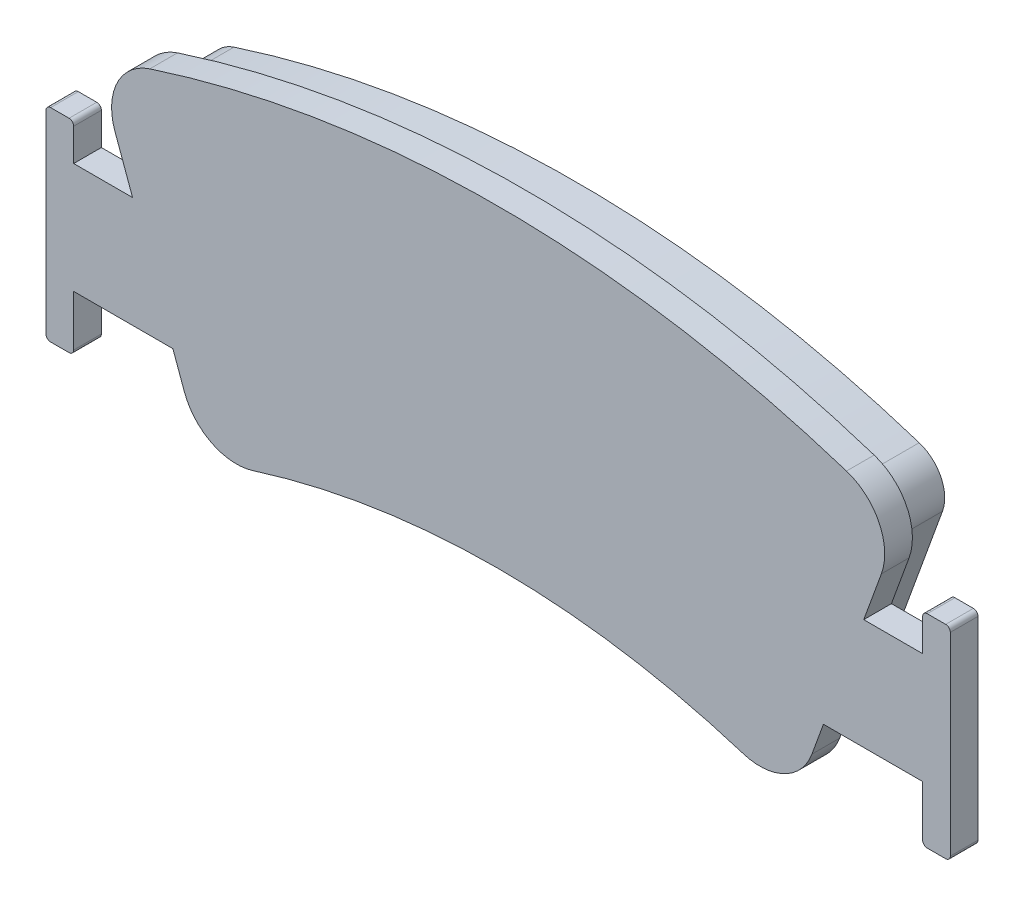
SolidWorks part; units mm, degrees
ref_plane "Płaszczyzna przednia" through (0, 0, 0) normal (0, 0, 1) x (1, 0, 0)
ref_plane "Płaszczyzna górna" through (0, 0, 0) normal (0, 1, 0) x (1, 0, 0)
ref_plane "Płaszczyzna prawa" through (0, 0, 0) normal (1, 0, 0) x (0, 0, -1)
sketch "Szkic1" plane through (0, 0, 0) normal (0, 0, 1) x (1, 0, 0)
  line L0 (-3.3117, 84.9355) -> (-2.9977, 76.8831)
  line L1 (0.9603, 74.1578) -> (23.3617, 81.7266)
  line L2 (57.7167, 62.4002) -> (52.2449, 56.4843)
  line L3 (53.1165, 51.7585) -> (74.3086, 41.2702)
  line L4 (84.9355, 3.3117) -> (76.8831, 2.9977)
  line L5 (74.1578, -0.9603) -> (81.7266, -23.3617)
  line L6 (62.4002, -57.7167) -> (56.4843, -52.2449)
  line L7 (51.7585, -53.1165) -> (41.2702, -74.3086)
  line L8 (3.3117, -84.9355) -> (2.9977, -76.8831)
  line L9 (-0.9603, -74.1578) -> (-23.3617, -81.7266)
  line L10 (-57.7167, -62.4002) -> (-52.2449, -56.4843)
  line L11 (-53.1165, -51.7585) -> (-74.3086, -41.2702)
  line L12 (-84.9355, -3.3117) -> (-76.8831, -2.9977)
  line L13 (-74.1578, 0.9603) -> (-81.7266, 23.3617)
  line L14 (-62.4002, 57.7167) -> (-56.4843, 52.2449)
  line L15 (-51.7585, 53.1165) -> (-41.2702, 74.3086)
  line L16 (0.9603, 74.1578) -> (-1.6342, 73.1454)
  line L17 (-2.9977, 74.077) -> (-2.9977, 76.8831)
  line L18 (53.1165, 51.7585) -> (50.5661, 52.8772)
  line L19 (50.2606, 54.5001) -> (52.2449, 56.4843)
  line L20 (74.1578, -0.9603) -> (73.1454, 1.6342)
  line L21 (74.077, 2.9977) -> (76.8831, 2.9977)
  line L22 (51.7585, -53.1165) -> (52.8772, -50.5661)
  line L23 (54.5001, -50.2606) -> (56.4843, -52.2449)
  line L24 (-0.9603, -74.1578) -> (1.6342, -73.1454)
  line L25 (2.9977, -74.077) -> (2.9977, -76.8831)
  line L26 (-53.1165, -51.7585) -> (-50.5661, -52.8772)
  line L27 (-50.2606, -54.5001) -> (-52.2449, -56.4843)
  line L28 (-74.1578, 0.9603) -> (-73.1454, -1.6342)
  line L29 (-74.077, -2.9977) -> (-76.8831, -2.9977)
  line L30 (-51.7585, 53.1165) -> (-52.8772, 50.5661)
  line L31 (-54.5001, 50.2606) -> (-56.4843, 52.2449)
  line L32 (-3.2338, 82.937) -> (-2.9977, 76.8831)
  line L33 (19.9378, 80.5697) -> (15.0444, 78.9164)
  line L34 (0.9603, 74.1578) -> (5.5705, 75.7155)
  line L35 (44.0396, 59.8465) -> (26.6236, 49.8436)
  line L36 (22.133, 52.2992) -> (21.2067, 71.3197)
  line L37 (25.5267, 74.1578) -> (43.8691, 65.1401)
  line L38 (70.4876, 34.3874) -> (77.0812, 15.0409)
  line L39 (73.4586, 11.1771) -> (54.0705, 16.4191)
  line L40 (52.6315, 21.3307) -> (65.426, 35.4352)
  line L41 (74.1578, -25.5267) -> (65.1401, -43.8691)
  line L42 (59.8465, -44.0396) -> (49.8436, -26.6236)
  line L43 (52.2992, -22.133) -> (71.3197, -21.2067)
  line L44 (34.3874, -70.4876) -> (15.0409, -77.0812)
  line L45 (11.1771, -73.4586) -> (16.4191, -54.0705)
  line L46 (21.3307, -52.6315) -> (35.4352, -65.426)
  line L47 (-25.5267, -74.1578) -> (-43.8691, -65.1401)
  line L48 (-44.0396, -59.8465) -> (-26.6236, -49.8436)
  line L49 (-22.133, -52.2992) -> (-21.2067, -71.3197)
  line L50 (-70.4876, -34.3874) -> (-77.0812, -15.0409)
  line L51 (-73.4586, -11.1771) -> (-54.0705, -16.4191)
  line L52 (-52.6315, -21.3307) -> (-65.426, -35.4352)
  line L53 (-74.1578, 25.5267) -> (-65.1401, 43.8691)
  line L54 (-59.8465, 44.0396) -> (-49.8436, 26.6236)
  line L55 (-52.2992, 22.133) -> (-71.3197, 21.2067)
  line L56 (-34.3874, 70.4876) -> (-15.0409, 77.0812)
  line L57 (-11.1771, 73.4586) -> (-16.4191, 54.0705)
  line L58 (-21.3307, 52.6315) -> (-35.4352, 65.426)
  circle A0 centre (0, 0) radius 120
  arc A2 (-62.4002, 57.7167) -> (-81.7266, 23.3617) centre (0, 0) ccw
  circle A3 centre (0, 50) radius 7
  circle A4 centre (50, 0) radius 7
  circle A5 centre (0, -50) radius 7
  circle A6 centre (-50, 0) radius 7
  circle A7 centre (0, 0) radius 35
  circle A8 centre (10.3075, 77.316) radius 5
  circle A9 centre (61.9591, 47.3822) radius 5
  circle A10 centre (77.316, -10.3075) radius 5
  circle A11 centre (47.3822, -61.9591) radius 5
  circle A12 centre (-10.3075, -77.316) radius 5
  circle A13 centre (-61.9591, -47.3822) radius 5
  circle A14 centre (-77.316, 10.3075) radius 5
  circle A15 centre (-47.3822, 61.9591) radius 5
  arc A16 (-2.9977, 76.8831) -> (0.9603, 74.1578) centre (0, 77) ccw
  arc A17 (52.2449, 56.4843) -> (53.1165, 51.7585) centre (54.4472, 54.4472) ccw
  arc A18 (76.8831, 2.9977) -> (74.1578, -0.9603) centre (77, 0) ccw
  arc A19 (56.4843, -52.2449) -> (51.7585, -53.1165) centre (54.4472, -54.4472) ccw
  arc A20 (2.9977, -76.8831) -> (-0.9603, -74.1578) centre (0, -77) ccw
  arc A21 (-52.2449, -56.4843) -> (-53.1165, -51.7585) centre (-54.4472, -54.4472) ccw
  arc A22 (-76.8831, -2.9977) -> (-74.1578, 0.9603) centre (-77, 0) ccw
  arc A23 (-56.4843, 52.2449) -> (-51.7585, 53.1165) centre (-54.4472, 54.4472) ccw
  arc A24 (-84.9355, -3.3117) -> (-74.3086, -41.2702) centre (0, 0) ccw
  arc A25 (-57.7167, -62.4002) -> (-23.3617, -81.7266) centre (0, 0) ccw
  arc A26 (3.3117, -84.9355) -> (41.2702, -74.3086) centre (0, 0) ccw
  arc A27 (62.4002, -57.7167) -> (81.7266, -23.3617) centre (0, 0) ccw
  arc A28 (84.9355, 3.3117) -> (74.3086, 41.2702) centre (0, 0) ccw
  arc A29 (57.7167, 62.4002) -> (23.3617, 81.7266) centre (0, 0) ccw
  arc A30 (-3.3117, 84.9355) -> (-41.2702, 74.3086) centre (0, 0) ccw
  arc A31 (19.9378, 80.5697) -> (56.3587, 60.9319) centre (0, 0) cw
  arc A32 (-1.6342, 73.1454) -> (-2.9977, 74.077) centre (-1.9977, 74.077) cw
  arc A33 (50.5661, 52.8772) -> (50.2606, 54.5001) centre (50.9678, 53.793) cw
  arc A34 (71.0696, 42.8732) -> (82.937, 3.2338) centre (0, 0) cw
  arc A35 (73.1454, 1.6342) -> (74.077, 2.9977) centre (74.077, 1.9977) cw
  arc A36 (80.5697, -19.9378) -> (60.9319, -56.3587) centre (0, 0) cw
  arc A37 (52.8772, -50.5661) -> (54.5001, -50.2606) centre (53.793, -50.9678) cw
  arc A38 (42.8732, -71.0696) -> (3.2338, -82.937) centre (0, 0) cw
  arc A39 (1.6342, -73.1454) -> (2.9977, -74.077) centre (1.9977, -74.077) cw
  arc A40 (-19.9378, -80.5697) -> (-56.3587, -60.9319) centre (0, 0) cw
  arc A41 (-50.5661, -52.8772) -> (-50.2606, -54.5001) centre (-50.9678, -53.793) cw
  arc A42 (-71.0696, -42.8732) -> (-82.937, -3.2338) centre (0, 0) cw
  arc A43 (-73.1454, -1.6342) -> (-74.077, -2.9977) centre (-74.077, -1.9977) cw
  arc A44 (-80.5697, 19.9378) -> (-60.9319, 56.3587) centre (0, 0) cw
  arc A45 (-52.8772, 50.5661) -> (-54.5001, 50.2606) centre (-53.793, 50.9678) cw
  arc A46 (-42.8732, 71.0696) -> (-3.2338, 82.937) centre (0, 0) cw
  arc A47 (15.0444, 78.9164) -> (5.5705, 75.7155) centre (10.3075, 77.316) ccw
  arc A48 (44.0396, 59.8465) -> (43.8691, 65.1401) centre (42.5455, 62.4479) ccw
  arc A49 (21.2067, 71.3197) -> (25.5267, 74.1578) centre (24.2031, 71.4656) cw
  arc A50 (26.6236, 49.8436) -> (22.133, 52.2992) centre (25.1294, 52.4451) cw
  arc A51 (65.426, 35.4352) -> (70.4876, 34.3874) centre (67.648, 33.4196) cw
  arc A52 (73.4586, 11.1771) -> (77.0812, 15.0409) centre (74.2416, 14.0731) ccw
  arc A53 (54.0705, 16.4191) -> (52.6315, 21.3307) centre (54.8535, 19.3151) cw
  arc A54 (71.3197, -21.2067) -> (74.1578, -25.5267) centre (71.4656, -24.2031) cw
  arc A55 (59.8465, -44.0396) -> (65.1401, -43.8691) centre (62.4479, -42.5455) ccw
  arc A56 (49.8436, -26.6236) -> (52.2992, -22.133) centre (52.4451, -25.1294) cw
  arc A57 (35.4352, -65.426) -> (34.3874, -70.4876) centre (33.4196, -67.648) cw
  arc A58 (11.1771, -73.4586) -> (15.0409, -77.0812) centre (14.0731, -74.2416) ccw
  arc A59 (16.4191, -54.0705) -> (21.3307, -52.6315) centre (19.3151, -54.8535) cw
  arc A60 (-21.2067, -71.3197) -> (-25.5267, -74.1578) centre (-24.2031, -71.4656) cw
  arc A61 (-44.0396, -59.8465) -> (-43.8691, -65.1401) centre (-42.5455, -62.4479) ccw
  arc A62 (-26.6236, -49.8436) -> (-22.133, -52.2992) centre (-25.1294, -52.4451) cw
  arc A63 (-65.426, -35.4352) -> (-70.4876, -34.3874) centre (-67.648, -33.4196) cw
  arc A64 (-73.4586, -11.1771) -> (-77.0812, -15.0409) centre (-74.2416, -14.0731) ccw
  arc A65 (-54.0705, -16.4191) -> (-52.6315, -21.3307) centre (-54.8535, -19.3151) cw
  arc A66 (-71.3197, 21.2067) -> (-74.1578, 25.5267) centre (-71.4656, 24.2031) cw
  arc A67 (-59.8465, 44.0396) -> (-65.1401, 43.8691) centre (-62.4479, 42.5455) ccw
  arc A68 (-49.8436, 26.6236) -> (-52.2992, 22.133) centre (-52.4451, 25.1294) cw
  arc A69 (-35.4352, 65.426) -> (-34.3874, 70.4876) centre (-33.4196, 67.648) cw
  arc A70 (-11.1771, 73.4586) -> (-15.0409, 77.0812) centre (-14.0731, 74.2416) ccw
  arc A71 (-16.4191, 54.0705) -> (-21.3307, 52.6315) centre (-19.3151, 54.8535) cw
  dimension "D1" = 240
  dimension "D2" = 14
  dimension "D3" = 170
  dimension "D5" = 70
  dimension "D6" = 10
  dimension "D10" = 77
  dimension "D12" = 3
  dimension "D11" = 2
  dimension "D14" = 1
  dimension "D16" = 3
  dimension "D4" = 4
  dimension "D7" = 50
  dimension "D8" = 78
  dimension "D9" = 8
  dimension "D13" = 8
  dimension "D15" = 8
  dimension "D17" = 8
sketch "Szkic2" plane through (0, 0, 0) normal (0, 0, 1) x (1, 0, 0)
  line L0 (0, 0) -> (-49.4404, 135.8364)
  line L1 (0, 0) -> (0, 158.8834)
  line L2 (-39.6507, 108.9395) -> (-32.1208, 88.2511)
  line L3 (0, 120) -> (0, 90)
  arc A0 (-35.9121, 98.6677) -> (0, 105) centre (0, 0) cw construction
  arc A1 (0, 120) -> (-37.1296, 114.1113) centre (0, 0) ccw
  arc A2 (0, 90) -> (-27.1551, 85.8056) centre (0, 0) ccw
  circle A5 centre (0, 0) radius 120 construction
  arc A6 (-27.1551, 85.8056) -> (-32.1208, 88.2511) centre (-28.362, 89.6192) cw
  arc A7 (-37.1296, 114.1113) -> (-39.6507, 108.9395) centre (-35.892, 110.3076) ccw
  point P6 (-18.2331, 103.4048)
  dimension "D4" = 105
  dimension "D5" = 4
  dimension "D1" = 20
  dimension "D2" = 30
  dimension "D3" = 20
extrude "Dodanie-wyciągnięcie1" add sketch "Szkic2" along normal blind 6.5 contours A1 A7 L0 A6 A2 L1 region at (-18.1572, 103.6045, 0)
sketch "Szkic3" plane through (0, 0, 6.5) normal (0, 0, 1) x (1, 0, 0)
  line L0 (-35.2496, 91) -> (-34.0002, 87.5671)
  line L2 (-49, 103) -> (-49, 85.5)
  line L3 (-48.5, 85) -> (-46.5, 85)
  line L4 (-46, 85.5) -> (-46, 91)
  line L5 (-46, 91) -> (-35.2496, 91)
  line L7 (-41.5301, 108.2555) -> (-39.6173, 103)
  line L9 (-39.6507, 108.9395) -> (-32.1208, 88.2511)
  line L10 (0, 90) -> (0, 120)
  line L12 (0, 90) -> (0, 120)
  line L13 (0, 120) -> (0, 122)
  line L14 (0, 122) -> (0, 88)
  line L15 (-39.6507, 108.9395) -> (-32.1208, 88.2511) construction
  line L16 (2, 87.9773) -> (2, 121.9836) construction
  line L17 (-39.6173, 103) -> (-46, 103)
  line L18 (-41.5301, 108.2555) -> (-34.0002, 87.5671) construction
  line L19 (-49, 103) -> (-49, 106.5)
  line L20 (-48.5, 107) -> (-46.5, 107)
  line L21 (-46, 106.5) -> (-46, 103)
  arc A0 (0, 122) -> (-37.7485, 116.0132) centre (0, 0) ccw
  arc A1 (-37.7485, 116.0132) -> (-41.5301, 108.2555) centre (-35.892, 110.3076) ccw
  arc A2 (-34.0002, 87.5671) -> (-26.5517, 83.8988) centre (-28.362, 89.6192) ccw
  arc A3 (0, 88) -> (-26.5517, 83.8988) centre (0, 0) ccw
  arc A4 (0, 120) -> (-37.1296, 114.1113) centre (0, 0) ccw
  arc A5 (-37.1296, 114.1113) -> (-39.6507, 108.9395) centre (-35.892, 110.3076) ccw
  arc A6 (-32.1208, 88.2511) -> (-27.1551, 85.8056) centre (-28.362, 89.6192) ccw
  arc A7 (0, 90) -> (-27.1551, 85.8056) centre (0, 0) ccw
  arc A12 (2, 121.9836) -> (-37.7485, 116.0132) centre (0, 0) ccw construction
  arc A13 (2, 87.9773) -> (-26.5517, 83.8988) centre (0, 0) ccw construction
  arc A14 (0, 90) -> (-27.1551, 85.8056) centre (0, 0) ccw construction
  arc A15 (-32.1208, 88.2511) -> (-27.1551, 85.8056) centre (-28.362, 89.6192) ccw construction
  arc A16 (-37.1296, 114.1113) -> (-39.6507, 108.9395) centre (-35.892, 110.3076) ccw construction
  arc A17 (0, 120) -> (-37.1296, 114.1113) centre (0, 0) ccw construction
  arc A18 (-46.5, 85) -> (-46, 85.5) centre (-46.5, 85.5) ccw
  arc A19 (-49, 85.5) -> (-48.5, 85) centre (-48.5, 85.5) ccw
  arc A20 (-46.5, 107) -> (-46, 106.5) centre (-46.5, 106.5) cw
  arc A21 (-49, 106.5) -> (-48.5, 107) centre (-48.5, 106.5) cw
  point P33 (-46, 85)
  point P36 (-49, 85)
  point P41 (-49, 107)
  arc M13 (0, 120) -> (-37.1296, 114.1113) centre (0, 0) ccw
  arc M14 (-37.1296, 114.1113) -> (-39.6507, 108.9395) centre (-35.892, 110.3076) ccw
  line M15 (-39.6507, 108.9395) -> (-32.1208, 88.2511)
  arc M16 (-32.1208, 88.2511) -> (-27.1551, 85.8056) centre (-28.362, 89.6192) ccw
  arc M17 (-27.1551, 85.8056) -> (0, 90) centre (0, 0) cw
  line M18 (0, 90) -> (0, 120)
  dimension "D10" = 0.5
  dimension "D3" = 12
  dimension "D4" = 6
  dimension "D5" = 3
  dimension "D6" = 18
  dimension "D7" = 49
  dimension "D8" = 17
  dimension "D9" = 4
  dimension "D1" = 0
  dimension "D2" = 2
extrude "Dodanie-wyciągnięcie2" add sketch "Szkic3" along normal blind 3 contours M18 M13 M14 M15 M16 M17 | A3 L14 L13 A0 A1 L7 L17 L2 L3 L4 L5 L0 A2 M17 M16 M15 M14 M13 region at (-40.6248, 91.6224, 6.5) region at (-18.1572, 103.6045, 6.5)
mirror "Lustro1" about plane through (0, 0, 0) normal (1, 0, 0) of "Dodanie-wyciągnięcie2", "Dodanie-wyciągnięcie1"
chamfer "Sfazowanie1" distance 1 angle 70 8 edges at (35.8858, 98.5953, 0) (30.1292, 86.0307, 0) (39.4875, 112.0603, 0) (0, 90, 0) (0, 120, 0) (-30.1292, 86.0307, 0) (-39.4875, 112.0603, 0) (-35.8858, 98.5953, 0) first distance on face at (35.8858, 98.5953, 3.25) first distance on face at (29.8836, 86.5295, 3.25) first distance on face at (38.9388, 111.7929, 3.25) first distance on face at (0, 87.9028, 3.25) first distance on face at (0, 117.0557, 3.25) first distance on face at (-29.8836, 86.5295, 3.25) first distance on face at (-38.9388, 111.7929, 3.25) first distance on face at (-35.8858, 98.5953, 3.25)
